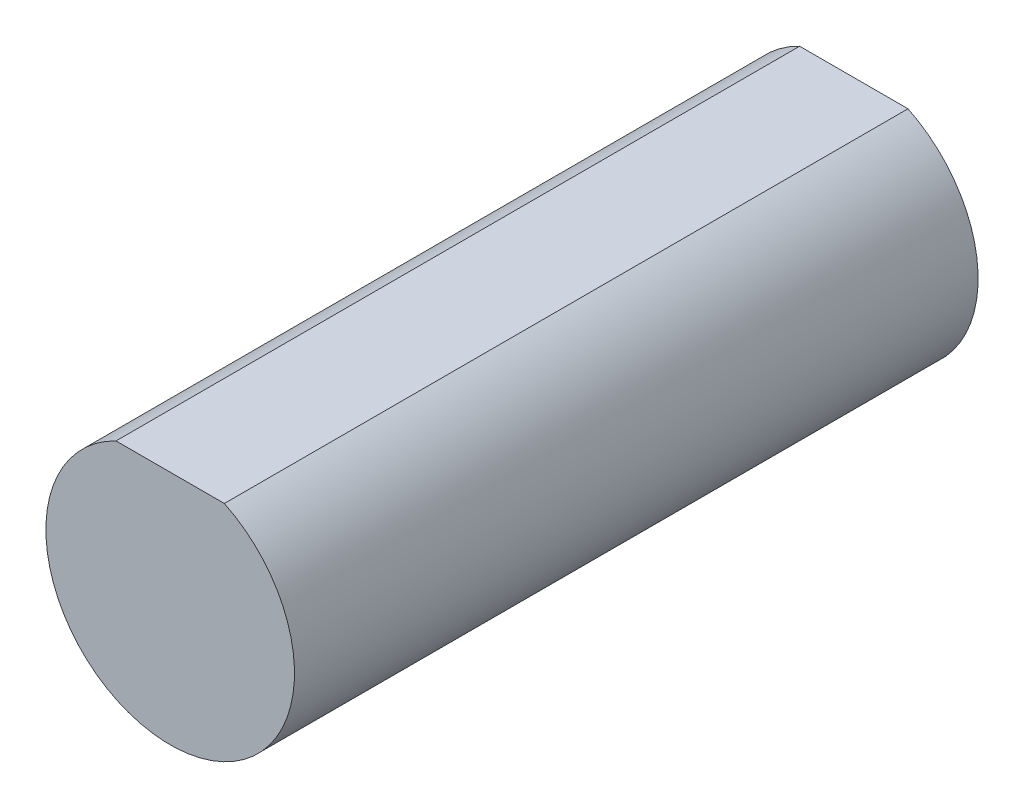
SolidWorks part; units mm, degrees
ref_plane "前视基准面" through (0, 0, 0) normal (0, 0, 1) x (1, 0, 0)
ref_plane "上视基准面" through (0, 0, 0) normal (0, 1, 0) x (1, 0, 0)
ref_plane "右视基准面" through (0, 0, 0) normal (1, 0, 0) x (0, 0, -1)
other "Configuration Table"
sketch "草图1" plane through (0, 0, 0) normal (0, 0, 1) x (1, 0, 0)
  circle A0 centre (0, 0) radius 10
  dimension "D1" = 20
extrude "凸台-拉伸1" add sketch "草图1" along normal blind 55
sketch "草图2" plane through (0, 0, 55) normal (0, 0, 1) x (1, 0, 0)
  line L0 (-4.3589, 9) -> (4.3589, 9)
  arc A0 (4.3589, 9) -> (-4.3589, 9) centre (0, 0) ccw
  dimension "D1" = 20
  dimension "D2" = 9
extrude "切除-拉伸1" cut sketch "草图2" against normal through all
